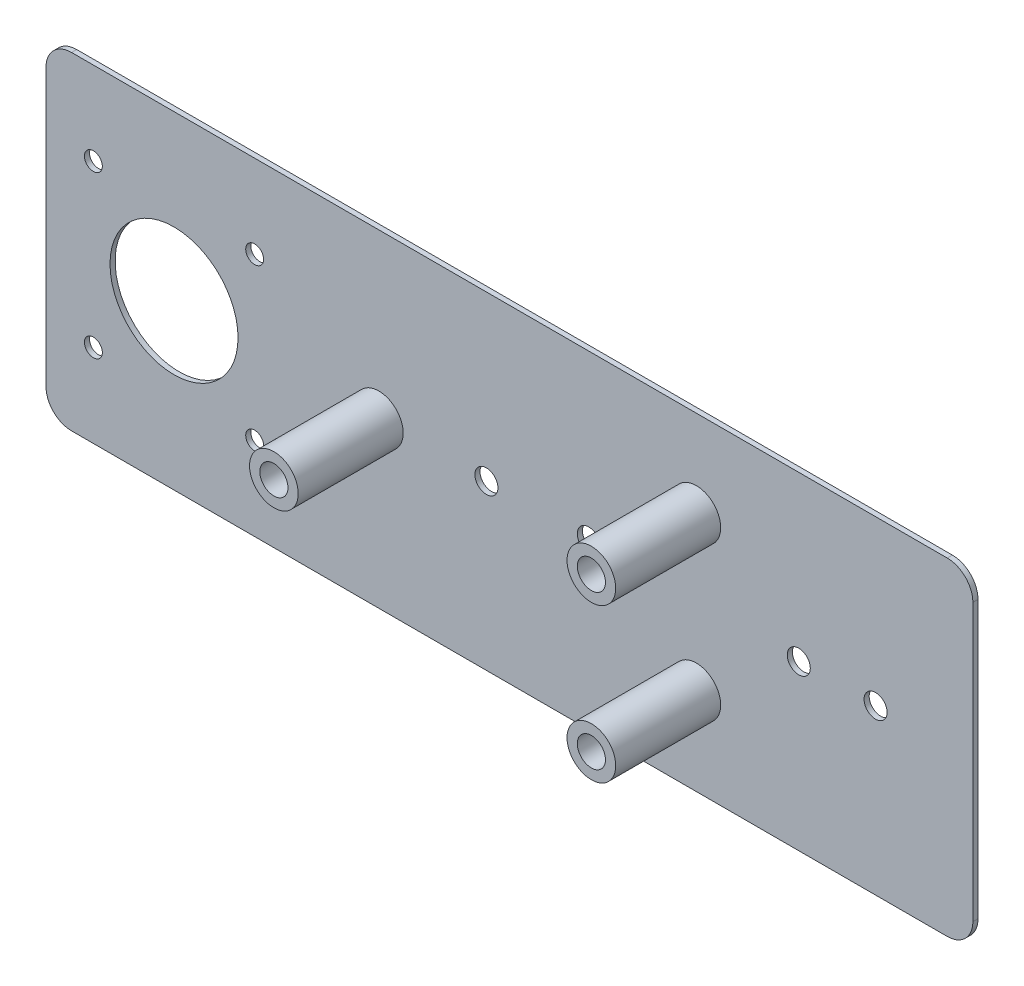
SolidWorks part; units mm, degrees
material "ABS PC"
ref_plane "Front Plane" through (0, 0, 0) normal (0, 0, 1) x (1, 0, 0)
ref_plane "Top Plane" through (0, 0, 0) normal (0, 1, 0) x (1, 0, 0)
ref_plane "Right Plane" through (0, 0, 0) normal (1, 0, 0) x (0, 0, -1)
sketch "Sketch1" plane through (0, 0, 0) normal (0, 0, 1) x (1, 0, 0)
  line L1 (-85.5, 32) -> (85.5, 32)
  line L2 (-90.5, 27) -> (-90.5, -27)
  line L3 (-85.5, -32) -> (85.5, -32)
  line L4 (90.5, 27) -> (90.5, -27)
  line L5 (-90.5, 32) -> (90.5, -32) construction
  line L6 (-90.5, -32) -> (90.5, 32) construction
  arc A0 (85.5, -32) -> (90.5, -27) centre (85.5, -27) ccw
  arc A1 (85.5, 32) -> (90.5, 27) centre (85.5, 27) cw
  arc A2 (-90.5, -27) -> (-85.5, -32) centre (-85.5, -27) ccw
  arc A3 (-85.5, 32) -> (-90.5, 27) centre (-85.5, 27) ccw
  point P0 (0, 0)
  dimension "D3" = 5
  dimension "D1" = 64
  dimension "D2" = 181
extrude "Boss-Extrude1" add sketch "Sketch1" along normal blind 37
sketch "Sketch2" plane through (0, 0, 37) normal (0, 0, 1) x (1, 0, 0)
  line L0 (-65.5, 0) -> (0, 0) construction
  line L1 (-49.75, 15.75) -> (-81.25, 15.75) construction
  line L2 (-49.75, 15.75) -> (-49.75, -15.75) construction
  line L3 (-49.75, -15.75) -> (-81.25, -15.75) construction
  line L4 (-81.25, 15.75) -> (-81.25, -15.75) construction
  line L5 (-49.75, 15.75) -> (-81.25, -15.75) construction
  line L6 (-49.75, -15.75) -> (-81.25, 15.75) construction
  line L7 (-90.5, 27) -> (-90.5, -27) construction
  line L8 (36.5, 15) -> (36.5, -15) construction
  line L9 (0, 0) -> (36.5, 0) construction
  line L10 (36.5, 0) -> (56.5, 0) construction
  circle A0 centre (-81.25, 15.75) radius 1.75
  circle A1 centre (-49.75, 15.75) radius 1.75
  circle A2 centre (-81.25, -15.75) radius 1.75
  circle A3 centre (-49.75, -15.75) radius 1.75
  circle A4 centre (-65.5, 0) radius 12.5
  circle A5 centre (36.5, 15) radius 2.75
  circle A6 centre (36.5, -15) radius 2.75
  circle A7 centre (-25.5, 0) radius 2.75
  circle A8 centre (56.5, 0) radius 2.25
  circle A9 centre (71.5, 0) radius 2.25
  point P0 (-65.5, 0)
  dimension "D1" = 3.5
  dimension "D4" = 25
  dimension "D5" = 5.5
  dimension "D10" = 4.5
  dimension "D11" = 15
  dimension "D2" = 31.5
  dimension "D3" = 25
  dimension "D6" = 30
  dimension "D7" = 127
  dimension "D8" = 62
  dimension "D9" = 20
extrude "Cut-Extrude1" cut sketch "Sketch2" against normal through all
sketch "Sketch3" plane through (0, 0, 37) normal (0, 0, 1) x (1, 0, 0)
  circle A3 centre (36.5, 15) radius 2.75 construction
  circle A4 centre (36.5, 15) radius 2.75
  circle A5 centre (36.5, 15) radius 4.75
  circle A6 centre (-25.5, 0) radius 2.75 construction
  circle A7 centre (36.5, -15) radius 2.75 construction
  circle A8 centre (-25.5, 0) radius 2.75
  circle A9 centre (36.5, -15) radius 2.75
  circle A10 centre (-25.5, 0) radius 4.75
  circle A11 centre (36.5, -15) radius 4.75
  dimension "D1" = 2
  dimension "D2" = 2
sketch "Sketch4" plane through (0, 0, 0) normal (0, 0, 1) x (1, 0, 0)
  line L0 (90.5, 0) -> (90.5, -10) construction
  line L1 (90.5, -27) -> (90.5, 27) construction
  line L2 (0, 0) -> (90.5, 0) construction
  line L3 (90.5, 10) -> (100.5, 10) construction
  line L4 (90.5, -10) -> (100.5, -10) construction
  line L5 (100.5, 2.25) -> (100.5, -2.25) construction
  line L6 (100.5, 10) -> (100.5, 2.25) construction
  line L7 (100.5, -2.25) -> (100.5, -10) construction
  line L8 (90.5, 10) -> (90.5, 0) construction
  arc A0 (100.5, -10) -> (100.5, 10) centre (100.5, 0) ccw construction
  arc A1 (100.5, 2.25) -> (100.5, -2.25) centre (100.5, 0) ccw construction
  arc A2 (100.5, -2.25) -> (100.5, 2.25) centre (100.5, 0) ccw construction
  dimension "D3" = 4.5
  dimension "D1" = 20
  dimension "D2" = 10
sketch "Sketch5" plane through (0, 0, 37) normal (0, 0, 1) x (1, 0, 0)
  line L0 (-25.5, 0) -> (36.5, 0) construction
  line L1 (36.5, 0) -> (36.5, -15) construction
  circle A0 centre (-4.5, 0) radius 2.25
  circle A1 centre (15.5, 0) radius 2.25
  point P10 (5.5, 0)
  dimension "D3" = 4.5
  dimension "D1" = 10
  dimension "D2" = 10
extrude "Cut-Extrude2" cut sketch "Sketch5" against normal through all
sketch "Sketch6" plane through (0, 0, 37) normal (0, 0, 1) x (1, 0, 0)
  line L0 (85.5, 32) -> (-85.5, 32) construction
  line L1 (-85.5, -29) -> (85.5, -29)
  line L2 (-87.5, -27) -> (-87.5, 27)
  line L3 (-85.5, 29) -> (85.5, 29)
  line L4 (87.5, -27) -> (87.5, 27)
  line L5 (-87.5, -29) -> (87.5, 29) construction
  line L6 (-87.5, 29) -> (87.5, -29) construction
  line L7 (90.5, -27) -> (90.5, 27) construction
  arc A0 (-87.5, 27) -> (-85.5, 29) centre (-85.5, 27) cw
  arc A1 (-85.5, -29) -> (-87.5, -27) centre (-85.5, -27) cw
  arc A2 (85.5, -29) -> (87.5, -27) centre (85.5, -27) ccw
  arc A3 (85.5, 29) -> (87.5, 27) centre (85.5, 27) cw
  point P0 (0, 0)
  dimension "D3" = 2
  dimension "D1" = 3
  dimension "D2" = 3
extrude "Cut-Extrude3" cut sketch "Sketch6" against normal blind 36
sketch "Sketch7" plane through (0, 0, 1) normal (0, 0, 1) x (1, 0, 0)
  circle A0 centre (-25.5, 0) radius 4.75
  circle A1 centre (-25.5, 0) radius 2.75 construction
  circle A2 centre (36.5, -15) radius 4.75
  circle A3 centre (36.5, 15) radius 4.75
  circle A4 centre (36.5, -15) radius 2.75 construction
  dimension "D1" = 2
  dimension "D2" = 2
  dimension "D3" = 9.5
extrude "Boss-Extrude2" add sketch "Sketch7" along normal blind 20.5
sketch "Sketch10" plane through (0, 0, 37) normal (0, 0, 1) x (1, 0, 0)
  line L0 (-85.5, -32) -> (85.5, -32) construction
  line L1 (-14.5, -32) -> (25.5, -32)
  line L2 (-14.5, -32) -> (-14.5, 32)
  line L3 (-14.5, 32) -> (25.5, 32)
  line L4 (25.5, -32) -> (25.5, 32)
  line L5 (-14.5, -32) -> (25.5, 32) construction
  line L6 (-14.5, 32) -> (25.5, -32) construction
  line L7 (85.5, 32) -> (-85.5, 32) construction
  line L8 (5.5, 0) -> (36.5, 0) construction
  line L9 (0, 0) -> (90.5, 0) construction
  line L10 (36.5, 0) -> (36.5, -15) construction
  point P0 (5.5, 0)
  dimension "D1" = 40
  dimension "D2" = 31
extrude "Cut-Extrude4" cut sketch "Sketch10" against normal blind 36
sketch "Sketch11" plane through (0, 0, 21.5) normal (0, 0, 1) x (1, 0, 0)
  circle A0 centre (36.5, -15) radius 2.75
  circle A1 centre (-25.5, 0) radius 2.75
  circle A2 centre (36.5, 15) radius 2.75
  dimension "D1" = 5.5
  dimension "D2" = 5.5
  dimension "D3" = 5.5
extrude "Cut-Extrude5" cut sketch "Sketch11" against normal through all
sketch "Sketch12" plane through (0, 0, 1) normal (0, 0, 1) x (1, 0, 0)
  line L0 (25.5, -29) -> (85.5, -29) construction
  line L1 (67.5, -29) -> (82.5, -29)
  line L2 (67.5, -29) -> (67.5, -19)
  line L3 (67.5, -19) -> (82.5, -19)
  line L4 (82.5, -29) -> (82.5, -19)
  line L5 (90.5, 0) -> (32.1507, 0) construction
  line L6 (0, 0) -> (90.5, 0) construction
  line L7 (67.5, 19) -> (82.5, 19)
  line L8 (82.5, 29) -> (82.5, 19)
  line L9 (67.5, 29) -> (82.5, 29)
  line L10 (67.5, 29) -> (67.5, 19)
  line L11 (87.5, -27) -> (87.5, 27) construction
  line L12 (87.5, -6) -> (67.5, -6)
  line L13 (87.5, -6) -> (87.5, -16)
  line L14 (87.5, -16) -> (67.5, -16)
  line L15 (67.5, -6) -> (67.5, -16)
  line L16 (87.5, 16) -> (67.5, 16)
  line L17 (67.5, 6) -> (67.5, 16)
  line L18 (87.5, 6) -> (67.5, 6)
  line L19 (87.5, 6) -> (87.5, 16)
  line L20 (87.5, -27) -> (87.5, 27) construction
  line L21 (-85.5, -29) -> (-14.5, -29) construction
  line L22 (-42.5, -29) -> (-32.5, -29)
  line L23 (-42.5, -29) -> (-42.5, -19)
  line L24 (-42.5, -19) -> (-32.5, -19)
  line L25 (-32.5, -29) -> (-32.5, -19)
  line L26 (-42.5, 19) -> (-32.5, 19)
  line L27 (-32.5, 29) -> (-32.5, 19)
  line L28 (-42.5, 29) -> (-32.5, 29)
  line L29 (-42.5, 29) -> (-42.5, 19)
  line L30 (-87.5, 27) -> (-87.5, -27) construction
  dimension "D1" = 15
  dimension "D2" = 5
  dimension "D3" = 10
  dimension "D4" = 20
  dimension "D5" = 3
  dimension "D6" = 10
  dimension "D7" = 10
  dimension "D8" = 10
  dimension "D9" = 45
extrude "Boss-Extrude3" add sketch "Sketch12" along normal through all
sketch "Sketch14" plane through (0, -16, 0) normal (0, -1, 0) x (1, 0, 0)
  line L3 (87.5, 37) -> (67.5, 37)
  line L4 (67.5, 37) -> (67.5, 3)
  line L5 (67.5, 3) -> (87.5, 37)
  dimension "D1" = 34
extrude "Cut-Extrude6" cut sketch "Sketch14" against normal blind 33
sketch "Sketch16" plane through (82.5, 0, 0) normal (1, 0, 0) x (0, 0, -1)
  line L0 (-37, -19) -> (-3, -19)
  line L1 (-3, -19) -> (-37, -29)
  line L2 (-37, -27) -> (-37, 27) construction
  line L3 (-37, -29) -> (-37, -19)
  dimension "D1" = 10
  dimension "D2" = 34
extrude "Cut-Extrude8" cut sketch "Sketch16" against normal blind 15
sketch "Sketch17" plane through (67.5, 0, 0) normal (-1, 0, 0) x (0, 0, 1)
  line L6 (37, 19) -> (1, 19)
  line L7 (1, 19) -> (37, 29)
  line L8 (37, 29) -> (37, 19)
extrude "Cut-Extrude9" cut sketch "Sketch17" against normal blind 15
sketch "Sketch18" plane through (-32.5, 0, 0) normal (1, 0, 0) x (0, 0, -1)
  line L0 (-37, -29) -> (-37, -19)
  line L1 (-37, -19) -> (-1, -19)
  line L2 (-1, -19) -> (-37, -29)
extrude "Cut-Extrude10" cut sketch "Sketch18" against normal blind 10
sketch "Sketch19" plane through (-32.5, 0, 0) normal (1, 0, 0) x (0, 0, -1)
  line L0 (-37, 29) -> (-1, 19)
  line L1 (-1, 19) -> (-37, 19)
  line L2 (-37, 19) -> (-37, 29)
extrude "Cut-Extrude11" cut sketch "Sketch19" against normal blind 10
sketch "Sketch20" plane through (-90.5, 0, 0) normal (-1, 0, 0) x (0, 0, 1)
  line L0 (37, 27) -> (37, -27) construction
  line L1 (33, 7.5) -> (27, 7.5)
  line L2 (33, 7.5) -> (33, -7.5)
  line L3 (33, -7.5) -> (27, -7.5)
  line L4 (27, 7.5) -> (27, -7.5)
  line L5 (33, 7.5) -> (27, -7.5) construction
  line L6 (33, -7.5) -> (27, 7.5) construction
  line L7 (0, 0) -> (37, 0) construction
  line L8 (37, -2.75) -> (37, 2.75) construction
  point P0 (30, 0)
  dimension "D1" = 4
  dimension "D2" = 15
  dimension "D3" = 6
extrude "Cut-Extrude12" cut sketch "Sketch20" against normal blind 3
sketch "Sketch21" plane through (0, 0, 37) normal (0, 0, 1) x (1, 0, 0)
  line L0 (-90.5, 27) -> (-90.5, -27) construction
  line L1 (-14.5, 32) -> (-90.5, 32)
  line L2 (-14.5, 32) -> (-14.5, -32)
  line L3 (-14.5, -32) -> (-90.5, -32)
  line L4 (-90.5, 32) -> (-90.5, -32)
  line L5 (-85.5, -32) -> (-14.5, -32) construction
  line L6 (90.5, -27) -> (90.5, 27) construction
  line L7 (-30.25, 4.75) -> (-20.75, 4.75)
  line L8 (-30.25, 4.75) -> (-30.25, -4.75)
  line L9 (-30.25, -4.75) -> (-20.75, -4.75)
  line L10 (-20.75, 4.75) -> (-20.75, -4.75)
  line L11 (-30.25, 4.75) -> (-20.75, -4.75) construction
  line L12 (-30.25, -4.75) -> (-20.75, 4.75) construction
  line L13 (25.5, 32) -> (90.5, 32)
  line L14 (25.5, 32) -> (25.5, -32)
  line L15 (25.5, -32) -> (90.5, -32)
  line L16 (90.5, 32) -> (90.5, -32)
  line L17 (25.5, -32) -> (85.5, -32) construction
  line L18 (31.75, -10.25) -> (41.25, -10.25)
  line L19 (31.75, -10.25) -> (31.75, -19.75)
  line L20 (31.75, -19.75) -> (41.25, -19.75)
  line L21 (41.25, -10.25) -> (41.25, -19.75)
  line L22 (31.75, -10.25) -> (41.25, -19.75) construction
  line L23 (31.75, -19.75) -> (41.25, -10.25) construction
  line L24 (31.75, 19.75) -> (41.25, 19.75)
  line L25 (31.75, 19.75) -> (31.75, 10.25)
  line L26 (31.75, 10.25) -> (41.25, 10.25)
  line L27 (41.25, 19.75) -> (41.25, 10.25)
  line L28 (31.75, 19.75) -> (41.25, 10.25) construction
  line L29 (31.75, 10.25) -> (41.25, 19.75) construction
  circle A0 centre (-25.5, 0) radius 4.75 construction
  circle A1 centre (-25.5, 0) radius 4.75 construction
  circle A3 centre (36.5, -15) radius 4.75 construction
  circle A4 centre (36.5, -15) radius 4.75 construction
  circle A5 centre (36.5, 15) radius 4.75 construction
  point P9 (-25.5, 0)
  point P26 (36.5, -15)
  point P32 (36.5, 15)
  point P44 (-14.5, 32)
  point P45 (31.75, 10.25)
  point P46 (-14.5, -32)
extrude "Cut-Extrude13" cut sketch "Sketch21" against normal up to surface (36 mm away) up to face at (-30.25, 0, 1)
